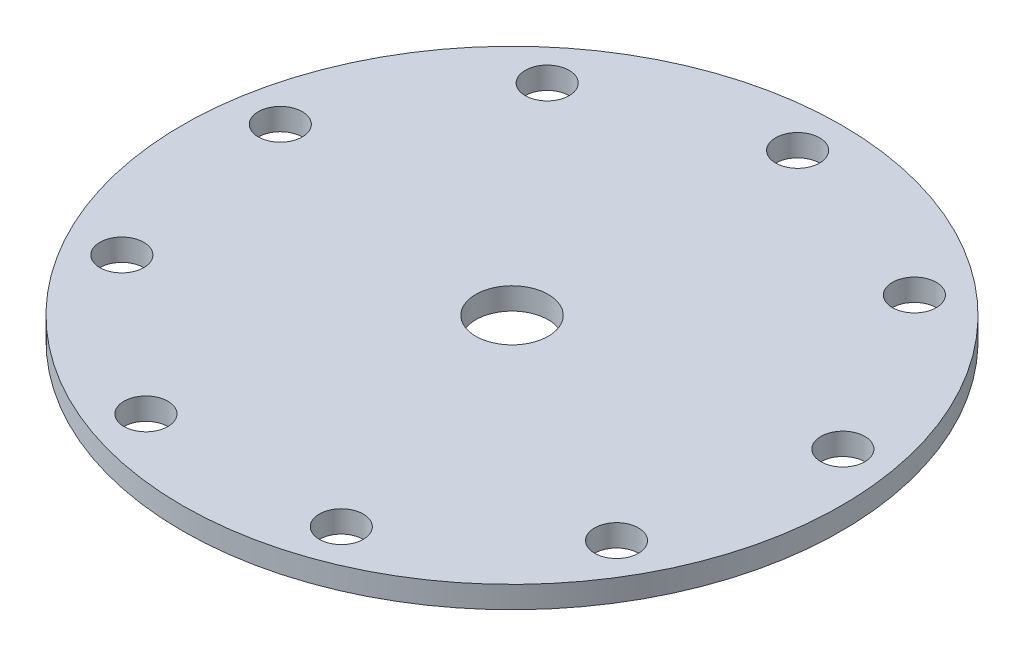
SolidWorks part; units mm, degrees
ref_plane "前视基准面" through (0, 0, 0) normal (0, 0, 1) x (1, 0, 0)
ref_plane "上视基准面" through (0, 0, 0) normal (0, 1, 0) x (1, 0, 0)
ref_plane "右视基准面" through (0, 0, 0) normal (1, 0, 0) x (0, 0, -1)
other "Configuration Table"
sketch "草图1" plane through (0, 0, 0) normal (0, 1, 0) x (1, 0, 0)
  line L0 (0, 52) -> (0, 0) construction
  circle A0 centre (0, 0) radius 60
  circle A1 centre (0, 52) radius 4
  circle A2 centre (33.425, 39.8343) radius 4
  circle A3 centre (51.21, 9.0297) radius 4
  circle A4 centre (45.0333, -26) radius 4
  circle A5 centre (17.785, -48.864) radius 4
  circle A6 centre (-17.785, -48.864) radius 4
  circle A7 centre (-45.0333, -26) radius 4
  circle A8 centre (-51.21, 9.0297) radius 4
  circle A9 centre (-33.425, 39.8343) radius 4
  circle A10 centre (0, 0) radius 6.6
  point P23 (0, 0)
  dimension "D1" = 120
  dimension "D2" = 8
  dimension "D4" = 9
  dimension "D5" = 52
  dimension "D7" = 13.2
  dimension "D3" = 52
  dimension "D6" = 35.5701
extrude "凸台-拉伸1" add sketch "草图1" along normal blind 4
